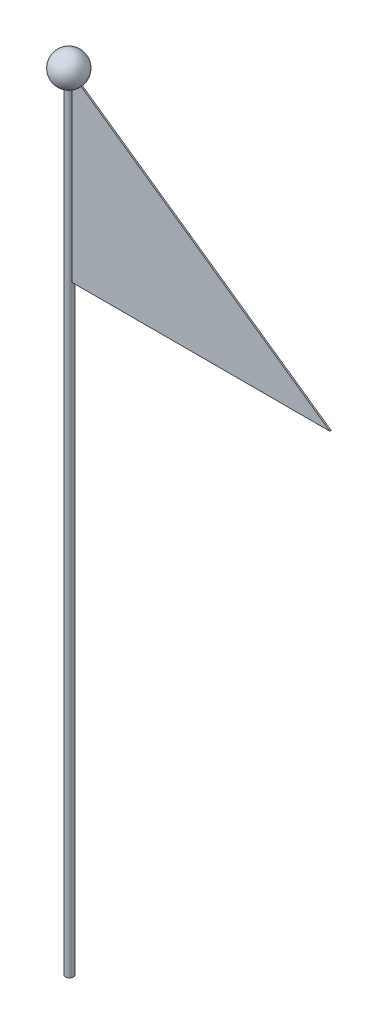
SolidWorks part; units mm, degrees
ref_plane "Front Plane" through (0, 0, 0) normal (0, 0, 1) x (1, 0, 0)
ref_plane "Top Plane" through (0, 0, 0) normal (0, 1, 0) x (1, 0, 0)
ref_plane "Right Plane" through (0, 0, 0) normal (1, 0, 0) x (0, 0, -1)
sketch "Sketch1" plane through (0, 0, 0) normal (0, 0, 1) x (1, 0, 0)
  line L0 (0, 0) -> (0, -140)
  line L1 (0, -140) -> (200, -140)
  line L2 (200, -140) -> (0, 0)
  dimension "D1" = 200
  dimension "D2" = 140
extrude "Boss-Extrude1" add sketch "Sketch1" along normal blind 0.5 and the other way blind 0.5
sketch "Sketch2" plane through (0, 0, 0) normal (0, 1, 0) x (1, 0, 0)
  circle A0 centre (0, 0.5) radius 3
  dimension "D1" = 6
extrude "Boss-Extrude2" add sketch "Sketch2" against normal blind 600
sketch "Sketch3" plane through (0, 0, 0) normal (0, 0, 1) x (1, 0, 0)
  line L0 (0, 12) -> (0, -12)
  arc A0 (0, 12) -> (0, -12) centre (0, 0) ccw
  point P4 (0, 0)
  dimension "D1" = 12
revolve "Revolve1" add sketch "Sketch3" angle 360 about L0
